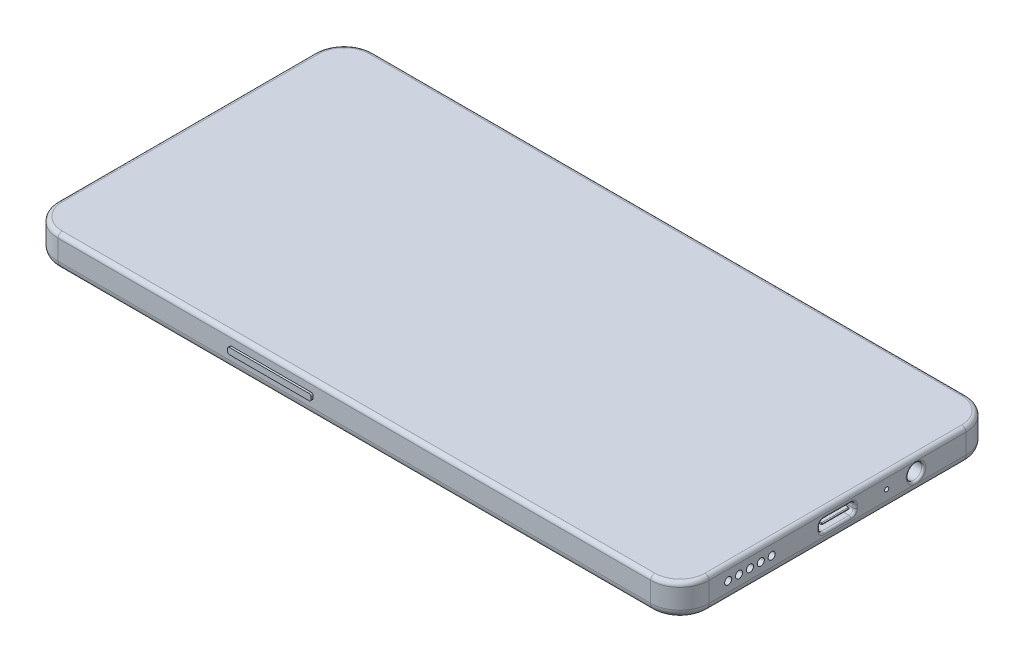
SolidWorks part; units mm, degrees
ref_plane "Front Plane" through (0, 0, 0) normal (0, 0, 1) x (1, 0, 0)
ref_plane "Top Plane" through (0, 0, 0) normal (0, 1, 0) x (1, 0, 0)
ref_plane "Right Plane" through (0, 0, 0) normal (1, 0, 0) x (0, 0, -1)
sketch "Sketch1" plane through (0, 0, 0) normal (0, 1, 0) x (1, 0, 0)
  line L1 (-77.85, -37.7) -> (77.85, -37.7)
  line L2 (-77.85, -37.7) -> (-77.85, 37.7)
  line L3 (-77.85, 37.7) -> (77.85, 37.7)
  line L4 (77.85, -37.7) -> (77.85, 37.7)
  line L5 (0, 37.7) -> (0, -37.7) construction
  line L6 (-77.85, 0) -> (77.85, 0) construction
  point P0 (0, 0)
  dimension "D1" = 155.7
  dimension "D2" = 75.4
extrude "Boss-Extrude1" add sketch "Sketch1" along normal blind 7.75
fillet "Fillet1" radius 7 4 edges at (-77.85, 3.875, -37.7) (77.85, 3.875, -37.7) (77.85, 3.875, 37.7) (-77.85, 3.875, 37.7)
fillet "Fillet2" radius 1 8 edges at (-75.7997, 7.75, 35.6497) (-77.85, 7.75, 0) (-75.7997, 7.75, -35.6497) (0, 7.75, -37.7) (75.7997, 7.75, -35.6497) (77.85, 7.75, 0) (75.7997, 7.75, 35.6497) (0, 7.75, 37.7)
fillet "Fillet3" radius 2 8 edges at (-75.7997, 0, 35.6497) (-77.85, 0, 0) (-75.7997, 0, -35.6497) (0, 0, -37.7) (75.7997, 0, -35.6497) (77.85, 0, 0) (75.7997, 0, 35.6497) (0, 0, 37.7)
sketch "Sketch2" plane through (0, 0, 0) normal (0, -1, 0) x (1, 0, 0)
  line L0 (-49.85, 0) -> (-59.85, 0) construction
  line L1 (-49.85, -5.575) -> (-59.85, -5.575)
  line L2 (-49.85, 5.575) -> (-59.85, 5.575)
  line L3 (-77.85, -30.7) -> (-77.85, 30.7) construction
  arc A0 (-49.85, -5.575) -> (-49.85, 5.575) centre (-49.85, 0) ccw
  arc A1 (-59.85, 5.575) -> (-59.85, -5.575) centre (-59.85, 0) ccw
  point P3 (-54.85, 0)
  point P8 (0, 0)
  point P9 (-48.962, 0)
  dimension "D1" = 10
  dimension "D3" = 18
  dimension "D2" = 11.15
extrude "Boss-Extrude2" add sketch "Sketch2" along normal blind 0.6
sketch "Sketch3" plane through (0, -0.6, 0) normal (0, -1, 0) x (1, 0, 0)
  line L0 (-49.85, 5.575) -> (-59.85, 5.575) construction
  line L3 (-59.85, -5.575) -> (-49.85, -5.575) construction
  circle A0 centre (-49.8619, 0.0106) radius 4
  circle A1 centre (-59.8619, 0) radius 4
  arc A4 (-59.85, 5.575) -> (-59.85, -5.575) centre (-59.85, 0) ccw construction
  arc A5 (-49.85, -5.575) -> (-49.85, 5.575) centre (-49.85, 0) ccw construction
  point P9 (-55.2799, 0)
  point P10 (-59.8672, 0)
  dimension "D1" = 8
  dimension "D2" = 8
  dimension "D3" = 10
  dimension "D4" = 5.575
  dimension "D5" = 5.575
  dimension "D6" = 0.0119
  dimension "D7" = 0.0159
extrude "Cut-Extrude1" cut sketch "Sketch3" against normal blind 0.1
sketch "Sketch4" plane through (0, -0.5, 0) normal (0, -1, 0) x (1, 0, 0)
  circle A0 centre (-49.8619, 0.0106) radius 2
  circle A1 centre (-59.8619, 0) radius 2
  dimension "D1" = 4
  dimension "D2" = 4
extrude "Cut-Extrude2" cut sketch "Sketch4" against normal blind 0.1
sketch "Sketch5" plane through (0, 0, 0) normal (0, -1, 0) x (1, 0, 0)
  line L0 (-39.8619, -2.6476) -> (-39.8619, 2.6476) construction
  line L1 (-41.1119, -2.6476) -> (-41.1119, 2.6476)
  line L2 (-38.6119, -2.6476) -> (-38.6119, 2.6476)
  line L3 (-75.85, 30.7) -> (-75.85, -30.7) construction
  line L4 (70.85, 35.7) -> (-70.85, 35.7) construction
  line L5 (-70.85, -35.7) -> (70.85, -35.7) construction
  arc A0 (-41.1119, -2.6476) -> (-38.6119, -2.6476) centre (-39.8619, -2.6476) ccw
  arc A1 (-38.6119, 2.6476) -> (-41.1119, 2.6476) centre (-39.8619, 2.6476) ccw
  circle A2 centre (-49.8619, 0.0106) radius 2 construction
  point P2 (-39.8619, 0)
  point P7 (0, 0)
  point P8 (0, 0)
  point P14 (-36.4988, -0.6391)
  point P15 (-36.4988, -0.5022)
  dimension "D1" = 5.2952
  dimension "D3" = 35.7
  dimension "D2" = 2.5
  dimension "D4" = 35.7
  dimension "D5" = 10
extrude "Cut-Extrude3" cut sketch "Sketch5" against normal blind 0.1
sketch "Sketch6" plane through (0, 0, 0) normal (0, -1, 0) x (1, 0, 0)
  line L0 (-38.6119, -2.6476) -> (-38.6119, 2.6476) construction
  line L1 (-29.2716, -6.25) -> (-36.1119, -6.25)
  line L2 (-29.2716, -6.25) -> (-29.2716, 6.25)
  line L3 (-29.2716, 6.25) -> (-36.1119, 6.25)
  line L4 (-36.1119, -6.25) -> (-36.1119, 6.25)
  line L5 (-32.6917, 6.25) -> (-32.6917, -6.25) construction
  line L6 (-29.2716, 0) -> (-36.1119, 0) construction
  line L7 (70.85, 35.7) -> (-70.85, 35.7) construction
  line L8 (-70.85, -35.7) -> (70.85, -35.7) construction
  point P0 (-32.6917, 0)
  dimension "D1" = 12.5
  dimension "D2" = 6.8403
  dimension "D3" = 2.5
  dimension "D4" = 29.45
  dimension "D5" = 29.45
extrude "Cut-Extrude4" cut sketch "Sketch6" against normal blind 0.1
fillet "Fillet4" radius 2 4 edges at (-29.2716, 0.05, 6.25) (-29.2716, 0.05, -6.25) (-36.1119, 0.05, 6.25) (-36.1119, 0.05, -6.25)
fillet "Fillet5" radius 0.5 8 edges at (-35.5261, 0.1, 5.6642) (-32.6917, 0.1, 6.25) (-29.8574, 0.1, 5.6642) (-29.2716, 0.1, 0) (-29.8574, 0.1, -5.6642) (-32.6917, 0.1, -6.25) (-35.5261, 0.1, -5.6642) (-36.1119, 0.1, 0)
sketch "Sketch7" plane through (0, 0, -37.7) normal (0, 0, 1) x (1, 0, 0)
  line L0 (-77.85, 2) -> (-77.85, 6.75) construction
  line L1 (-17.85, 3.375) -> (-29.85, 3.375)
  line L2 (-17.85, 3.375) -> (-17.85, 5.375)
  line L3 (-17.85, 5.375) -> (-29.85, 5.375)
  line L4 (-29.85, 3.375) -> (-29.85, 5.375)
  line L5 (-23.85, 5.375) -> (-23.85, 3.375) construction
  line L6 (-17.85, 4.375) -> (-29.85, 4.375) construction
  line L9 (-70.85, 2) -> (70.85, 2) construction
  line L10 (70.85, 6.75) -> (-70.85, 6.75) construction
  point P0 (-23.85, 4.375)
  point P6 (-77.85, 4.375)
  dimension "D1" = 60
  dimension "D2" = 2
  dimension "D3" = 1.375
  dimension "D4" = 1.375
  dimension "D5" = 12
extrude "Boss-Extrude3" add sketch "Sketch7" along normal blind 0.2 and the other way blind 0.2
fillet "Fillet6" radius 1 4 edges at (-17.85, 3.375, -37.8) (-17.85, 5.375, -37.8) (-29.85, 3.375, -37.8) (-29.85, 5.375, -37.8)
sketch "Sketch8" plane through (0, 0, -37.7) normal (0, 0, -1) x (-1, 0, 0)
  line L0 (48.115, 4.375) -> (39.115, 4.375) construction
  line L1 (48.115, 3.475) -> (39.115, 3.475)
  line L2 (48.115, 5.275) -> (39.115, 5.275)
  line L3 (-70.85, 2) -> (70.85, 2) construction
  line L5 (70.85, 6.75) -> (-70.85, 6.75) construction
  arc A0 (48.115, 3.475) -> (48.115, 5.275) centre (48.115, 4.375) ccw
  arc A1 (39.115, 5.275) -> (39.115, 3.475) centre (39.115, 4.375) ccw
  point P2 (43.615, 4.375)
  dimension "D1" = 9
  dimension "D2" = 2.375
  dimension "D3" = 2.375
extrude "Cut-Extrude5" cut sketch "Sketch8" against normal blind 0.5
sketch "Sketch9" plane through (0, 0, -37.2) normal (0, 0, -1) x (-1, 0, 0)
  line L0 (47.9183, 4.375) -> (39.5183, 4.375) construction
  line L1 (47.9183, 3.475) -> (39.5183, 3.475)
  line L2 (47.9183, 5.275) -> (39.5183, 5.275)
  line L3 (39.115, 3.475) -> (48.115, 3.475) construction
  line L4 (48.115, 5.275) -> (39.115, 5.275) construction
  arc A0 (47.9183, 3.475) -> (47.9183, 5.275) centre (47.9183, 4.375) ccw
  arc A1 (39.5183, 5.275) -> (39.5183, 3.475) centre (39.5183, 4.375) ccw
  point P4 (43.7183, 4.375)
  point P9 (44.0884, 4.3914)
  point P12 (43.7183, 4.1416)
  dimension "D1" = 8.4
extrude "Boss-Extrude4" add sketch "Sketch9" along normal blind 0.6
fillet "Fillet7" radius 0.1 4 edges at (-43.7183, 3.475, -37.8) (-38.6183, 4.375, -37.8) (-43.7183, 5.275, -37.8) (-48.8183, 4.375, -37.8)
sketch "Sketch11" plane through (77.85, 0, 0) normal (1, 0, 0) x (0, 0, -1)
  line L0 (30.7, 6.75) -> (-30.7, 6.75) construction
  line L1 (4.25, 5.75) -> (-4.25, 5.75)
  line L2 (4.25, 5.75) -> (4.25, 3)
  line L3 (4.25, 3) -> (-4.25, 3)
  line L4 (-4.25, 5.75) -> (-4.25, 3)
  line L5 (0, 3) -> (0, 5.75) construction
  line L6 (4.25, 4.375) -> (-4.25, 4.375) construction
  line L7 (-30.7, 2) -> (30.7, 2) construction
  line L8 (30.7, 2) -> (30.7, 6.75) construction
  line L9 (-30.7, 6.75) -> (-30.7, 2) construction
  point P0 (0, 4.375)
  dimension "D1" = 8.5
  dimension "D2" = 2.75
  dimension "D3" = 1
  dimension "D4" = 1
  dimension "D5" = 26.45
  dimension "D6" = 26.45
extrude "Cut-Extrude6" cut sketch "Sketch11" against normal blind 6.5
fillet "Fillet8" radius 1 4 edges at (74.6, 5.75, 4.25) (74.6, 5.75, -4.25) (74.6, 3, 4.25) (74.6, 3, -4.25)
sketch "Sketch12" plane through (71.35, 0, 0) normal (1, 0, 0) x (0, 0, -1)
  line L0 (-3.25, 3) -> (3.25, 3) construction
  line L1 (3.3225, 4.575) -> (-3.1775, 4.575)
  line L2 (3.3225, 4.575) -> (3.3225, 4.175)
  line L3 (3.3225, 4.175) -> (-3.1775, 4.175)
  line L4 (-3.1775, 4.575) -> (-3.1775, 4.175)
  line L5 (0.0725, 4.175) -> (0.0725, 4.575) construction
  line L6 (3.3225, 4.375) -> (-3.1775, 4.375) construction
  line L7 (3.25, 5.75) -> (-3.25, 5.75) construction
  point P0 (0.0725, 4.375)
  point P6 (0.0725, 4.5809)
  dimension "D1" = 0.4
  dimension "D2" = 1.175
  dimension "D3" = 1.175
extrude "Boss-Extrude5" add sketch "Sketch12" along normal blind 6
fillet "Fillet9" radius 0.5 8 edges at (77.85, 4.375, -4.25) (77.85, 5.4571, -3.9571) (77.85, 5.75, 0) (77.85, 5.4571, 3.9571) (77.85, 4.375, 4.25) (77.85, 3.2929, 3.9571) (77.85, 3, 0) (77.85, 3.2929, -3.9571)
sketch "Sketch13" plane through (77.85, 0, 0) normal (1, 0, 0) x (0, 0, -1)
  line L0 (-4.75, 4) -> (-4.75, 4.75) construction
  line L1 (-30.7, 2) -> (30.7, 2) construction
  line L2 (30.7, 6.75) -> (-30.7, 6.75) construction
  circle A0 centre (-15.75, 4.375) radius 0.85
  circle A1 centre (-18.35, 4.375) radius 0.85
  circle A2 centre (-20.95, 4.375) radius 0.85
  circle A3 centre (-23.55, 4.375) radius 0.85
  circle A4 centre (-26.15, 4.375) radius 0.85
  point P16 (23.5492, 4.5716)
  point P17 (18.2921, 4.5664)
  point P18 (15.75, 4.5664)
  point P19 (18.3209, 4.9546)
  point P20 (18.3209, 4.9546)
  point P21 (26.0871, 4.4175)
  point P22 (20.8917, 4.5664)
  point P23 (0, 0)
  point P24 (18.3209, 4.9546)
  dimension "D1" = 1.7
  dimension "D2" = 1.7
  dimension "D3" = 1.7
  dimension "D4" = 1.7
  dimension "D5" = 1.7
  dimension "D6" = 2.6
  dimension "D7" = 2.6
  dimension "D8" = 2.6
  dimension "D9" = 2.6
  dimension "D10" = 11
  dimension "D11" = 2.375
  dimension "D12" = 2.375
  dimension "D13" = 2.375
  dimension "D14" = 2.375
  dimension "D15" = 2.375
  dimension "D16" = 2.375
extrude "Cut-Extrude7" cut sketch "Sketch13" against normal blind 6
sketch "Sketch14" plane through (77.85, 0, 0) normal (1, 0, 0) x (0, 0, -1)
  line L0 (-30.7, 2) -> (30.7, 2) construction
  line L1 (30.7, 6.75) -> (-30.7, 6.75) construction
  line L3 (4.75, 4.75) -> (4.75, 4) construction
  circle A0 centre (18.75, 4.375) radius 1.85
  point P2 (-21.9922, 4.511)
  dimension "D1" = 3.7
  dimension "D2" = 2.375
  dimension "D3" = 2.375
  dimension "D4" = 14
extrude "Cut-Extrude8" cut sketch "Sketch14" against normal blind 14
fillet "Fillet10" radius 0.5 1 edges at (77.85, 4.375, -20.6)
fillet "Fillet12" radius 0.2 4 edges at (77.35, 4.575, -0.0725) (77.35, 4.375, -3.3225) (77.35, 4.175, -0.0725) (77.35, 4.375, 3.1775)
sketch "Sketch15" plane through (77.85, 0, 0) normal (1, 0, 0) x (0, 0, -1)
  line L0 (30.7, 6.75) -> (-30.7, 6.75) construction
  line L1 (4.75, 4.75) -> (4.75, 4) construction
  circle A0 centre (11.75, 4.375) radius 0.5
  circle A1 centre (18.75, 4.375) radius 2.35 construction
  dimension "D1" = 2.375
  dimension "D2" = 7
  dimension "D3" = 7
  dimension "D4" = 1
extrude "Cut-Extrude9" cut sketch "Sketch15" against normal blind 6
sketch "Sketch16" plane through (-77.85, 0, 0) normal (-1, 0, 0) x (0, 0, 1)
  line L0 (30.7, 6.75) -> (-30.7, 6.75) construction
  line L1 (-37.7, 2) -> (-37.7, 6.75) construction
  circle A0 centre (-16.7, 4.375) radius 0.5
  dimension "D1" = 1
  dimension "D2" = 2.375
  dimension "D3" = 21
extrude "Cut-Extrude10" cut sketch "Sketch16" against normal blind 6
sketch "Sketch18" plane through (0, 0, 37.7) normal (0, 0, 1) x (1, 0, 0)
  line L0 (-70.85, 2) -> (70.85, 2) construction
  line L1 (-29.85, 5.125) -> (-9.85, 5.125)
  line L2 (-29.85, 5.125) -> (-29.85, 3.625)
  line L3 (-29.85, 3.625) -> (-9.85, 3.625)
  line L4 (-9.85, 5.125) -> (-9.85, 3.625)
  line L5 (-19.85, 3.625) -> (-19.85, 5.125) construction
  line L6 (-29.85, 4.375) -> (-9.85, 4.375) construction
  line L7 (70.85, 6.75) -> (-70.85, 6.75) construction
  line L9 (-77.85, 2) -> (-77.85, 6.75) construction
  point P0 (-19.85, 4.375)
  point P4 (-42.0759, 4.1974)
  dimension "D1" = 1.5
  dimension "D2" = 48
  dimension "D3" = 20
  dimension "D4" = 1.625
  dimension "D5" = 1.625
extrude "Boss-Extrude6" add sketch "Sketch18" along normal blind 0.5
fillet "Fillet14" radius 0.5 4 edges at (-9.85, 3.625, 37.95) (-29.85, 3.625, 37.95) (-29.85, 5.125, 37.95) (-9.85, 5.125, 37.95)
